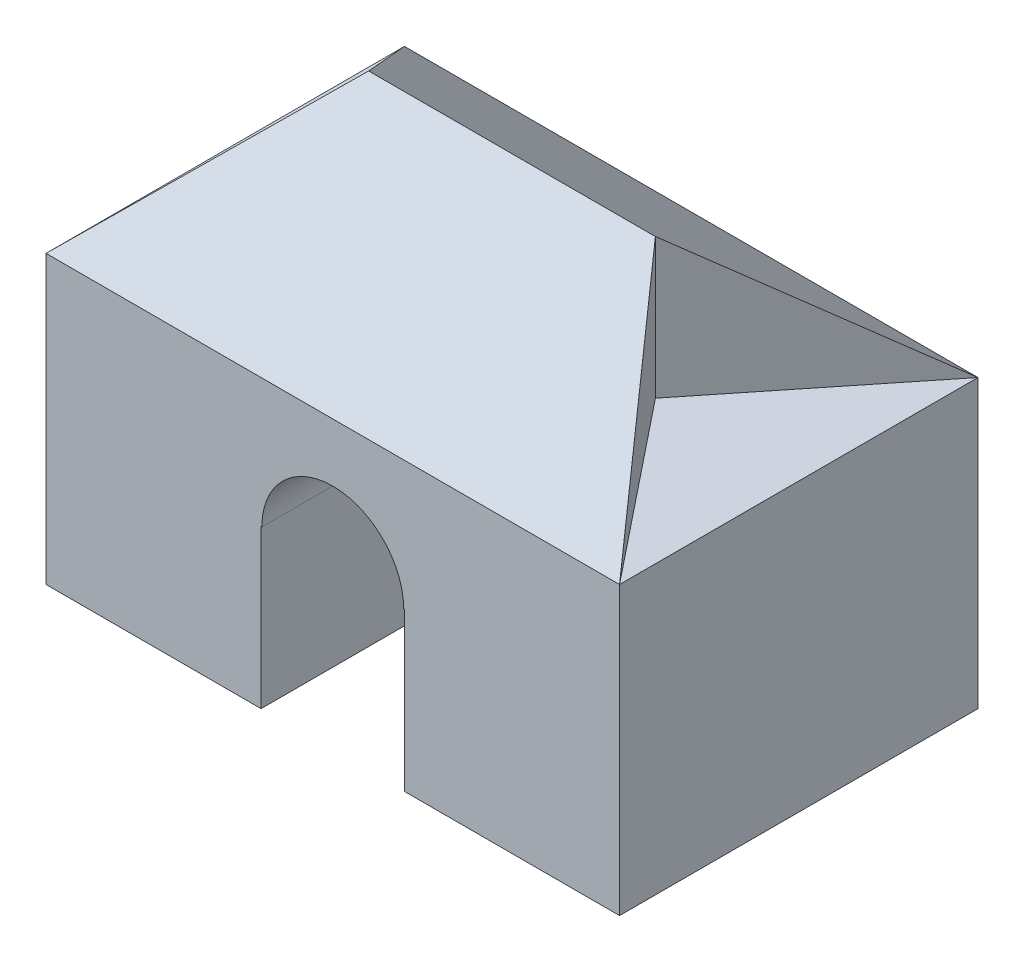
SolidWorks part; units mm, degrees
ref_plane "Alzado" through (0, 0, 0) normal (0, 0, 1) x (1, 0, 0)
ref_plane "Planta" through (0, 0, 0) normal (0, 1, 0) x (1, 0, 0)
ref_plane "Vista lateral" through (0, 0, 0) normal (1, 0, 0) x (0, 0, -1)
sketch "Croquis1" plane through (0, 0, 0) normal (0, 1, 0) x (1, 0, 0)
  line L1 (-200, 125) -> (200, 125)
  line L2 (-200, 125) -> (-200, -125)
  line L3 (-200, -125) -> (200, -125)
  line L4 (200, 125) -> (200, -125)
  line L5 (-200, 125) -> (200, -125) construction
  line L6 (-200, -125) -> (200, 125) construction
  point P0 (0, 0)
  dimension "D1" = 250
  dimension "D2" = 400
extrude "Saliente-Extruir1" add sketch "Croquis1" along normal blind 200
sketch "Croquis2" plane through (0, 0, 125) normal (0, 0, 1) x (1, 0, 0)
  line L0 (0, -1004.566) -> (0, 0) construction
  line L1 (-50, 0) -> (50, 0)
  line L3 (-50, 109.9898) -> (-49.4648, 109.9898)
  line L4 (50, 0) -> (50, 109.9898)
  line L5 (-50, 0) -> (-50, 109.9898)
  line L6 (-200, 0) -> (200, 0) construction
  line L7 (0, 109.9898) -> (0, 50004.566) construction
  line L8 (49.4648, 109.9898) -> (50, 109.9898)
  arc A0 (49.4648, 109.9898) -> (-49.4648, 109.9898) centre (0, 109.9898) ccw
  point P12 (0, 0)
  dimension "D1" = 150
extrude "Cortar-Extruir1" cut sketch "Croquis2" against normal blind 115
sketch "Croquis4" plane through (0, 200, 0) normal (0, 1, 0) x (1, 0, 0)
  line L0 (100, 0) -> (-100, 0) construction
  line L2 (-200, 125) -> (-100, 0)
  line L3 (-200, 125) -> (-200, -125) construction
  line L4 (-200, -125) -> (-100, 0)
  line L5 (200, -125) -> (100, 0)
  line L6 (200, 125) -> (100, 0)
  line L7 (-100, 0) -> (100, 0)
  line M6 (200, 125) -> (-200, 125)
  line M8 (-200, -125) -> (200, -125)
  dimension "D1" = 100
extrude "Saliente-Extruir2" add sketch "Croquis4" along normal blind 100 contours L2 L7 L6 M6 | L7 L4 L5 M8 region at (0, 200, -69.4444) region at (0, 200, 69.4444)
chamfer "Chaflán1" distance 100 angle 52 1 edges at (0, 300, 125) first distance on face at (0, 124.1187, 125)
chamfer "Chaflán2" distance 100 angle 52 1 edges at (0, 300, -125) first distance on face at (0, 166.6667, -125)
